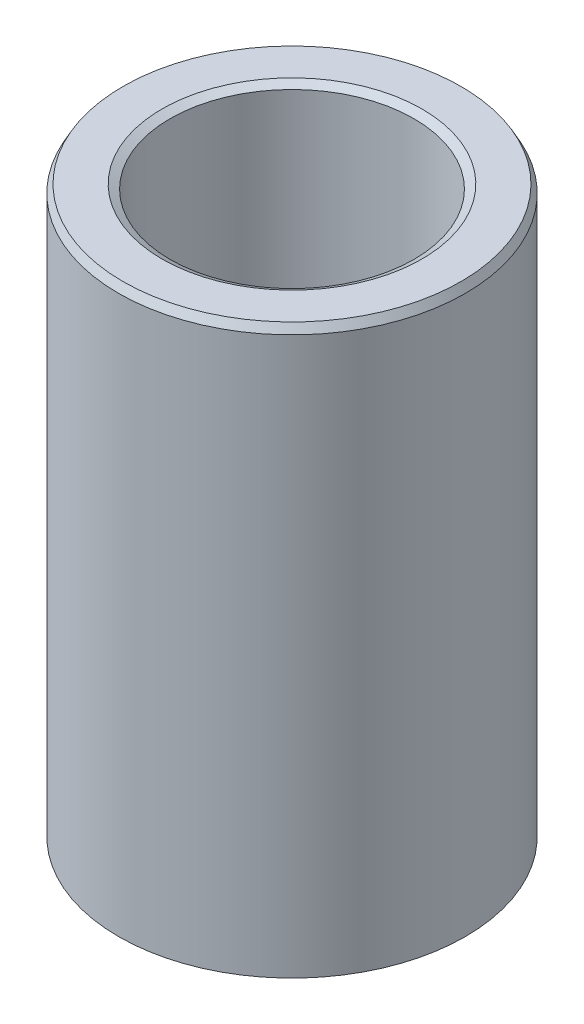
SolidWorks part; units mm, degrees
ref_plane "Front Plane" through (0, 0, 0) normal (0, 0, 1) x (1, 0, 0)
ref_plane "Top Plane" through (0, 0, 0) normal (0, 1, 0) x (1, 0, 0)
ref_plane "Right Plane" through (0, 0, 0) normal (1, 0, 0) x (0, 0, -1)
sketch "Sketch1" plane through (0, 0, 0) normal (0, 1, 0) x (1, 0, 0)
  circle A0 centre (0, 0) radius 40
  dimension "SLEEVE_OD" = 80
extrude "Boss-Extrude1" add sketch "Sketch1" along normal blind 131.3807
sketch "Sketch2" plane through (0, 0, 0) normal (0, 1, 0) x (1, 0, 0)
  circle A0 centre (0, 0) radius 28.133
  dimension "BORE_D" = 56.2661
extrude "Cut-Extrude1" cut sketch "Sketch2" along normal through all
chamfer "Chamfer1" distance 1.8575 angle 28.567 4 edges at (0, 131.3807, 28.133) (0, 0, 28.133) (0, 0, 40) (0, 131.3807, 40) first distance on face at (0, 131.3807, 28.133) first distance on face at (0, 0, 28.133) first distance on face at (0, 131.3807, 40)
